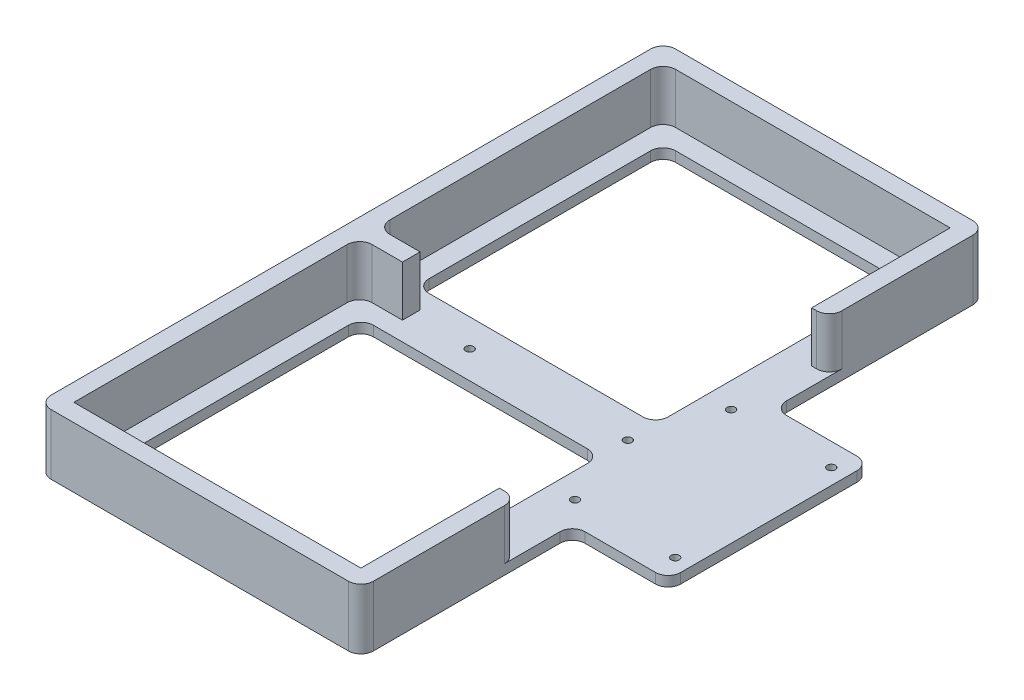
SolidWorks part; units mm, degrees
ref_plane "Front Plane" through (0, 0, 0) normal (0, 0, 1) x (1, 0, 0)
ref_plane "Top Plane" through (0, 0, 0) normal (0, 1, 0) x (1, 0, 0)
ref_plane "Right Plane" through (0, 0, 0) normal (1, 0, 0) x (0, 0, -1)
sketch "Sketch1" plane through (0, 0, 0) normal (0, 1, 0) x (1, 0, 0)
  line L0 (-62.8, 0) -> (0, 0) construction
  line L1 (0, 0) -> (0, 50000) construction
  line L2 (10, 31) -> (49.8, 31) construction
  line L3 (10, -31) -> (49.8, -31) construction
  line L4 (0, 11) -> (-95, 11)
  line L6 (0, 11) -> (0, 40)
  line L7 (18, 40) -> (56, 40)
  line L8 (56, 40) -> (56, -40)
  line L9 (0, -11) -> (0, -40)
  line L10 (18, -40) -> (56, -40)
  line L11 (0, -11) -> (-95, -11)
  line L12 (-95, 11) -> (-95, 109)
  line L13 (-95, 109) -> (0, 109)
  line L14 (0, 109) -> (0, 40)
  line L15 (18, 40) -> (18, 124)
  line L16 (18, 124) -> (-110, 124)
  line L17 (-110, 124) -> (-110, 22.9046)
  line L18 (0, -109) -> (0, -40)
  line L19 (18, -40) -> (18, -124)
  line L20 (18, -124) -> (-110, -124)
  line L21 (-95, -109) -> (0, -109)
  line L22 (-95, -11) -> (-95, -109)
  line L23 (-110, -124) -> (-110, -22.9046)
  line L24 (-110, 22.9046) -> (-110, -22.9046)
  line L25 (-20.1555, 92) -> (-79.1555, 92) construction
  line L26 (-79.1555, -92) -> (-20.1555, -92) construction
  line L27 (0, 0) -> (-50000, 0) construction
  circle A0 centre (0, 0) radius 1.6
  circle A1 centre (-62.8, 0) radius 1.6
  circle A2 centre (10, 31) radius 1.6
  circle A3 centre (49.8, 31) radius 1.6
  circle A4 centre (49.8, -31) radius 1.6
  circle A5 centre (10, -31) radius 1.6
  point P22 (56, 0)
  point P25 (-95, 0)
  dimension "D1" = 3.2
  dimension "D2" = 3.2
  dimension "D6" = 3.2
  dimension "D7" = 3.2
  dimension "D3" = 62.8
  dimension "D4" = 10
  dimension "D5" = 31
  dimension "D8" = 39.8
  dimension "D9" = 22
  dimension "D10" = 80
  dimension "D11" = 56
  dimension "D12" = 95
  dimension "D13" = 18
  dimension "D14" = 15
  dimension "D15" = 15
  dimension "D16" = 15
  dimension "D17" = 17
  dimension "D18" = 17
extrude "Boss-Extrude1" add sketch "Sketch1" along normal mid plane 4
sketch "Sketch2" plane through (0, 2, 0) normal (0, 1, 0) x (1, 0, 0)
  line L0 (18, 124) -> (-110, 124)
  line L1 (-110, 124) -> (-110, -124)
  line L2 (-110, 124) -> (-110, -124) construction
  line L5 (-103, 117) -> (11, 117)
  line L6 (18, 40) -> (18, 124) construction
  line L7 (18, 117) -> (18, 124)
  line L8 (0, 0) -> (50000, 0) construction
  line L9 (18, -117) -> (18, -124)
  line L11 (18, -124) -> (-110, -124)
  line L12 (-103, 117) -> (-103, 3.5)
  line L13 (-103, 3.5) -> (-86, 3.5)
  line L14 (-86, 3.5) -> (-86, -3.5)
  line L15 (-103, -3.5) -> (-86, -3.5)
  line L16 (-103, -117) -> (-103, -3.5)
  line L17 (18, 117) -> (18, 62)
  line L18 (18, 62) -> (11, 62)
  line L19 (11, 62) -> (11, 117)
  line L20 (56, 40) -> (18, 40) construction
  line L21 (18, -62) -> (11, -62)
  line L22 (18, -117) -> (18, -62)
  line L23 (11, -62) -> (11, -117)
  line L24 (-103, -117) -> (11, -117)
  point P19 (-103, 0)
  point P20 (-110, 0)
  point P24 (-86, 0)
  dimension "D2" = 7
  dimension "D1" = 7
  dimension "D3" = 17
  dimension "D4" = 7
  dimension "D5" = 7
  dimension "D6" = 22
extrude "Boss-Extrude2" add sketch "Sketch2" along normal blind 20
fillet "Fillet1" radius 5 21 edges at (56, 0, -40) (56, 0, 40) (18, 0, -40) (18, 0, 40) (18, 10, -124) (18, 10, 124) (-110, 10, -124) (0, 0, -109) (0, 0, -11) (-103, 12, -117) (-95, 0, -109) (-95, 0, -11) (0, 0, 109) (0, 0, 11) (-103, 12, -3.5) (-103, 12, 3.5) (-95, 0, 11) (-95, 0, 109) (-110, 10, 124) (18, 12, -62) (18, 12, 62)
equation "\"D2@Sketch1\"=\"D1@Sketch1\""
equation "\"D6@Sketch1\"=\"D2@Sketch1\""
equation "\"D7@Sketch1\"=\"D2@Sketch1\""
equation "\"D2@Sketch2\"=\"D5@Sketch2\""
equation "\"D15@Sketch1\"=\"D14@Sketch1\""
equation "\"D4@Sketch2\"=\"D5@Sketch2\""
